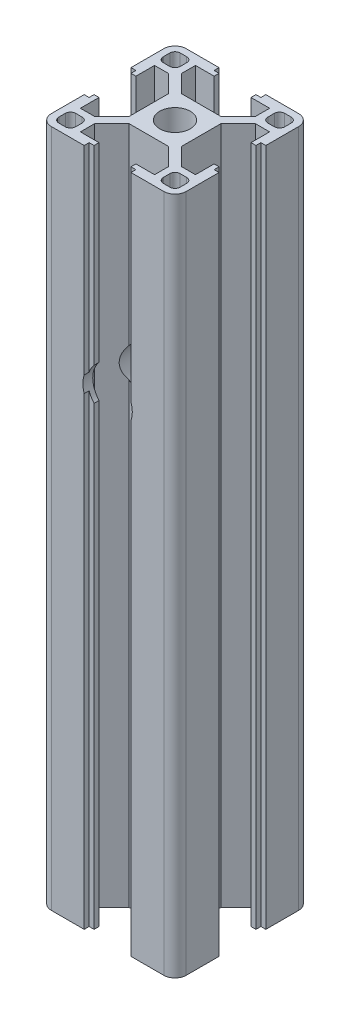
SolidWorks part; units mm, degrees
ref_plane "Front Plane" through (0, 0, 0) normal (0, 0, 1) x (1, 0, 0)
ref_plane "Top Plane" through (0, 0, 0) normal (0, 1, 0) x (1, 0, 0)
ref_plane "Right Plane" through (0, 0, 0) normal (1, 0, 0) x (0, 0, -1)
ref_plane "Plane1" through (0, 100, 0) normal (0, 1, 0) x (1, 0, 0)
sketch "Sketch1" plane through (0, 100, 0) normal (0, 1, 0) x (1, 0, 0)
  line L0 (28.5, -25.9) -> (28.5, -27.35)
  line L1 (27.35, -28.5) -> (25.9, -28.5)
  line L2 (24.75, -27.35) -> (24.75, -25.9)
  line L3 (25.9, -24.75) -> (27.35, -24.75)
  line L4 (1.5, -27.35) -> (1.5, -25.9)
  line L5 (2.65, -24.75) -> (4.1, -24.75)
  line L6 (5.25, -25.9) -> (5.25, -27.35)
  line L7 (4.1, -28.5) -> (2.65, -28.5)
  line L8 (2.65, -1.5) -> (4.1, -1.5)
  line L9 (5.25, -2.65) -> (5.25, -4.1)
  line L10 (4.1, -5.25) -> (2.65, -5.25)
  line L11 (1.5, -4.1) -> (1.5, -2.65)
  line L12 (28.5, -2.65) -> (28.5, -4.1)
  line L13 (27.35, -5.25) -> (25.9, -5.25)
  line L14 (24.75, -4.1) -> (24.75, -2.65)
  line L15 (25.9, -1.5) -> (27.35, -1.5)
  line L16 (27.5, 0) -> (20.2, 0)
  line L17 (20.2, 0) -> (20.2, -1.1)
  line L18 (20.2, -1.1) -> (19.1, -1.1)
  line L19 (19.1, -1.1) -> (19.1, -2.2)
  line L20 (19.1, -2.2) -> (23.25, -2.2)
  line L21 (23.25, -2.2) -> (23.25, -5.3358)
  line L22 (23.25, -5.3358) -> (19.3858, -9.2)
  line L23 (19.3858, -9.2) -> (10.6142, -9.2)
  line L24 (10.6142, -9.2) -> (6.75, -5.3358)
  line L25 (6.75, -5.3358) -> (6.75, -2.2)
  line L26 (6.75, -2.2) -> (10.9, -2.2)
  line L27 (10.9, -2.2) -> (10.9, -1.1)
  line L28 (10.9, -1.1) -> (9.8, -1.1)
  line L29 (9.8, -1.1) -> (9.8, 0)
  line L30 (9.8, 0) -> (2.5, 0)
  line L31 (0, -2.5) -> (0, -9.8)
  line L32 (0, -9.8) -> (1.1, -9.8)
  line L33 (1.1, -9.8) -> (1.1, -10.9)
  line L34 (1.1, -10.9) -> (2.2, -10.9)
  line L35 (2.2, -10.9) -> (2.2, -6.75)
  line L36 (2.2, -6.75) -> (5.3358, -6.75)
  line L37 (5.3358, -6.75) -> (9.2, -10.6142)
  line L38 (9.2, -10.6142) -> (9.2, -19.3858)
  line L39 (9.2, -19.3858) -> (5.3358, -23.25)
  line L40 (5.3358, -23.25) -> (2.2, -23.25)
  line L41 (2.2, -23.25) -> (2.2, -19.1)
  line L42 (2.2, -19.1) -> (1.1, -19.1)
  line L43 (1.1, -19.1) -> (1.1, -20.2)
  line L44 (1.1, -20.2) -> (0, -20.2)
  line L45 (0, -20.2) -> (0, -27.5)
  line L46 (2.5, -30) -> (9.8, -30)
  line L47 (9.8, -30) -> (9.8, -28.9)
  line L48 (9.8, -28.9) -> (10.9, -28.9)
  line L49 (10.9, -28.9) -> (10.9, -27.8)
  line L50 (10.9, -27.8) -> (6.75, -27.8)
  line L51 (6.75, -27.8) -> (6.75, -24.6642)
  line L52 (6.75, -24.6642) -> (10.6142, -20.8)
  line L53 (10.6142, -20.8) -> (19.3858, -20.8)
  line L54 (19.3858, -20.8) -> (23.25, -24.6642)
  line L55 (23.25, -24.6642) -> (23.25, -27.8)
  line L56 (23.25, -27.8) -> (19.1, -27.8)
  line L57 (19.1, -27.8) -> (19.1, -28.9)
  line L58 (19.1, -28.9) -> (20.2, -28.9)
  line L59 (20.2, -28.9) -> (20.2, -30)
  line L60 (20.2, -30) -> (27.5, -30)
  line L61 (30, -27.5) -> (30, -20.2)
  line L62 (30, -20.2) -> (28.9, -20.2)
  line L63 (28.9, -20.2) -> (28.9, -19.1)
  line L64 (28.9, -19.1) -> (27.8, -19.1)
  line L65 (27.8, -19.1) -> (27.8, -23.25)
  line L66 (27.8, -23.25) -> (24.6642, -23.25)
  line L67 (24.6642, -23.25) -> (20.8, -19.3858)
  line L68 (20.8, -19.3858) -> (20.8, -10.6142)
  line L69 (20.8, -10.6142) -> (24.6642, -6.75)
  line L70 (24.6642, -6.75) -> (27.8, -6.75)
  line L71 (27.8, -6.75) -> (27.8, -10.9)
  line L72 (27.8, -10.9) -> (28.9, -10.9)
  line L73 (28.9, -10.9) -> (28.9, -9.8)
  line L74 (28.9, -9.8) -> (30, -9.8)
  line L75 (30, -9.8) -> (30, -2.5)
  arc A0 (27.35, -24.75) -> (28.5, -25.9) centre (27.35, -25.9) cw
  arc A1 (28.5, -27.35) -> (27.35, -28.5) centre (27.35, -27.35) cw
  arc A2 (25.9, -28.5) -> (24.75, -27.35) centre (25.9, -27.35) cw
  arc A3 (24.75, -25.9) -> (25.9, -24.75) centre (25.9, -25.9) cw
  arc A4 (2.65, -28.5) -> (1.5, -27.35) centre (2.65, -27.35) cw
  arc A5 (1.5, -25.9) -> (2.65, -24.75) centre (2.65, -25.9) cw
  arc A6 (4.1, -24.75) -> (5.25, -25.9) centre (4.1, -25.9) cw
  arc A7 (5.25, -27.35) -> (4.1, -28.5) centre (4.1, -27.35) cw
  arc A8 (1.5, -2.65) -> (2.65, -1.5) centre (2.65, -2.65) cw
  arc A9 (4.1, -1.5) -> (5.25, -2.65) centre (4.1, -2.65) cw
  arc A10 (5.25, -4.1) -> (4.1, -5.25) centre (4.1, -4.1) cw
  arc A11 (2.65, -5.25) -> (1.5, -4.1) centre (2.65, -4.1) cw
  arc A12 (27.35, -1.5) -> (28.5, -2.65) centre (27.35, -2.65) cw
  arc A13 (28.5, -4.1) -> (27.35, -5.25) centre (27.35, -4.1) cw
  arc A14 (25.9, -5.25) -> (24.75, -4.1) centre (25.9, -4.1) cw
  arc A15 (24.75, -2.65) -> (25.9, -1.5) centre (25.9, -2.65) cw
  circle A16 centre (15, -15) radius 3.4
  arc A17 (30, -2.5) -> (27.5, 0) centre (27.5, -2.5) ccw
  arc A18 (2.5, 0) -> (0, -2.5) centre (2.5, -2.5) ccw
  arc A19 (0, -27.5) -> (2.5, -30) centre (2.5, -27.5) ccw
  arc A20 (27.5, -30) -> (30, -27.5) centre (27.5, -27.5) ccw
extrude "Boss-Extrude1" add sketch "Sketch1" against normal blind 151
sketch "Sketch2" plane through (0, 0, 20.8) normal (0, 0, 1) x (1, 0, 0)
  line L0 (15, 76.8101) -> (15, 31.1851) construction
  circle A0 centre (15, 76.8101) radius 3.125
  circle A1 centre (15, 53.9976) radius 5.5
  circle A2 centre (15, 31.1851) radius 3.125
  point P6 (6.6279, 57.7781)
  point P7 (15, 53.9976)
  dimension "D2" = 6.25
  dimension "D3" = 6.25
  dimension "D4" = 11
  dimension "D1" = 45.625
extrude "Cut-Extrude2" cut sketch "Sketch2" against normal through all both and the other way through all
